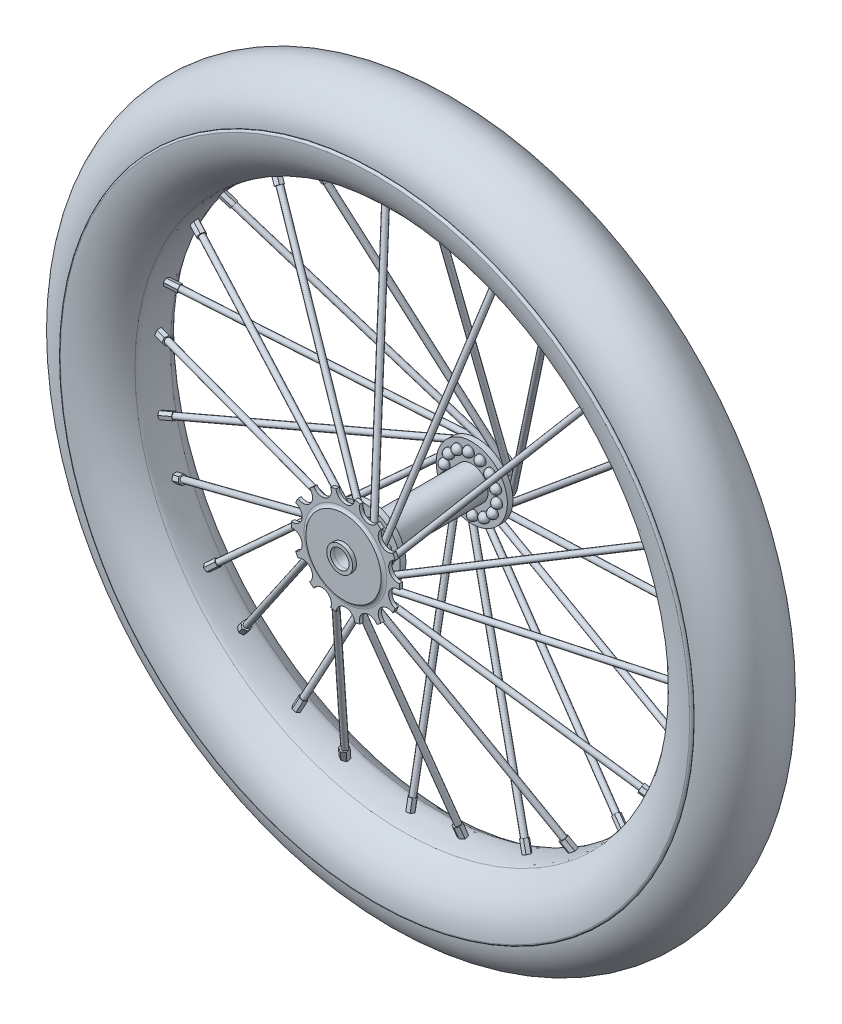
SolidWorks part; units mm, degrees
ref_plane "Front Plane" through (0, 0, 0) normal (0, 0, 1) x (1, 0, 0)
ref_plane "Top Plane" through (0, 0, 0) normal (0, 1, 0) x (1, 0, 0)
ref_plane "Right Plane" through (0, 0, 0) normal (1, 0, 0) x (0, 0, -1)
sketch "Sketch1" plane through (0, 0, 0) normal (1, 0, 0) x (0, 0, -1)
  line L0 (0, 144.78) -> (0, 0) construction
  line L1 (0, 0) -> (80.3154, 0) construction
  line L2 (0, 144.78) -> (0, 170.18) construction
  arc A0 (-22.86, 170.18) -> (22.86, 170.18) centre (0, 170.18) cw
  arc A1 (-22.86, 170.18) -> (-24.892, 170.18) centre (-23.876, 170.18) ccw
  arc A2 (22.86, 170.18) -> (24.892, 170.18) centre (23.876, 170.18) cw
  spline S0 degree 3 poles (-24.892, 170.18) (-24.6538, 159.1982) (-19.5696, 150.8197) (-9.6393, 145.0444) knots 0 0 0 0 1 1 1 1
  spline S1 degree 3 poles (24.892, 170.18) (24.6538, 159.1982) (19.5696, 150.8197) (9.6393, 145.0444) knots 0 0 0 0 1 1 1 1
  spline S2 degree 3 poles (-9.6393, 145.0444) (-7.0831, 143.5577) (7.0625, 143.5457) (9.6393, 145.0444) knots 0 0 0 0 1 1 1 1
  point P12 (0, 143.9249)
  dimension "D3" = 22.86
  dimension "D4" = 1.016
  dimension "D1" = 144.78
  dimension "D2" = 25.4
  dimension "D5" = 0.8551
revolve "Revolve1" add sketch "Sketch1" angle 360 about L1
sketch "Sketch2" plane through (0, 0, 0) normal (0, 0, 1) x (1, 0, 0)
  circle A0 centre (0, 0) radius 8.89
  circle A1 centre (0, 0) radius 5.08
  dimension "D1" = 10.16
  dimension "D2" = 17.78
extrude "Boss-Extrude1" add sketch "Sketch2" along normal blind 38.1 and the other way blind 38.1 separate body
sketch "Sketch3" plane through (0, 0, 38.1) normal (0, 0, 1) x (1, 0, 0)
  line L0 (5.0608, -28.7683) -> (7.9225, -28.1151)
  arc A0 (19.3366, 21.8934) -> (17.0417, 23.7235) centre (0, 0) ccw
  arc A1 (-5.0608, 28.7683) -> (5.0608, 28.7683) centre (0, 29.21) ccw
  arc A2 (7.9225, 28.1151) -> (17.0417, 23.7235) centre (12.6737, 26.3173) ccw
  arc A3 (19.3366, 21.8934) -> (25.6473, 13.9801) centre (22.8373, 18.2121) ccw
  arc A4 (26.9209, 11.3354) -> (29.1731, 1.4677) centre (28.4776, 6.4998) ccw
  arc A5 (29.1731, -1.4677) -> (26.9209, -11.3354) centre (28.4776, -6.4998) ccw
  arc A6 (25.6473, -13.9801) -> (19.3366, -21.8934) centre (22.8373, -18.2121) ccw
  arc A7 (17.0417, -23.7235) -> (7.9225, -28.1151) centre (12.6737, -26.3173) ccw
  arc A8 (5.0608, -28.7683) -> (-5.0608, -28.7683) centre (0, -29.21) ccw
  arc A9 (-7.9225, -28.1151) -> (-17.0417, -23.7235) centre (-12.6737, -26.3173) ccw
  arc A10 (-19.3366, -21.8934) -> (-25.6473, -13.9801) centre (-22.8373, -18.2121) ccw
  arc A11 (-26.9209, -11.3354) -> (-29.1731, -1.4677) centre (-28.4776, -6.4998) ccw
  arc A12 (-29.1731, 1.4677) -> (-26.9209, 11.3354) centre (-28.4776, 6.4998) ccw
  arc A13 (-25.6473, 13.9801) -> (-19.3366, 21.8934) centre (-22.8373, 18.2121) ccw
  arc A14 (-17.0417, 23.7235) -> (-7.9225, 28.1151) centre (-12.6737, 26.3173) ccw
  arc A15 (26.9209, 11.3354) -> (25.6473, 13.9801) centre (0, 0) ccw
  arc A16 (29.1731, -1.4677) -> (29.1731, 1.4677) centre (0, 0) ccw
  arc A17 (25.6473, -13.9801) -> (26.9209, -11.3354) centre (0, 0) ccw
  arc A18 (17.0417, -23.7235) -> (19.3366, -21.8934) centre (0, 0) ccw
  arc A19 (-7.9225, -28.1151) -> (-5.0608, -28.7683) centre (0, 0) ccw
  arc A20 (-19.3366, -21.8934) -> (-17.0417, -23.7235) centre (0, 0) ccw
  arc A21 (-26.9209, -11.3354) -> (-25.6473, -13.9801) centre (0, 0) ccw
  arc A22 (-29.1731, 1.4677) -> (-29.1731, -1.4677) centre (0, 0) ccw
  arc A23 (-25.6473, 13.9801) -> (-26.9209, 11.3354) centre (0, 0) ccw
  arc A24 (-17.0417, 23.7235) -> (-19.3366, 21.8934) centre (0, 0) ccw
  arc A25 (-5.0608, 28.7683) -> (-7.9225, 28.1151) centre (0, 0) ccw
  arc A26 (7.9225, 28.1151) -> (5.0608, 28.7683) centre (0, 0) ccw
  circle A27 centre (0, 0) radius 5.08
  dimension "D1" = 58.42
  dimension "D2" = 10.16
  dimension "D3" = 14
extrude "Boss-Extrude2" add sketch "Sketch3" along normal blind 3.81
sketch "Sketch4" plane through (0, 0, 38.1) normal (0, 0, -1) x (-1, 0, 0)
  circle A0 centre (0, 0) radius 11.43
  circle A1 centre (0, 0) radius 5.08 construction
  circle A2 centre (0, 0) radius 5.08
  dimension "D1" = 22.86
extrude "Boss-Extrude3" add sketch "Sketch4" along normal blind 3.81
sketch "Sketch5" plane through (0, 0, 34.29) normal (0, 0, -1) x (-1, 0, 0)
  circle A0 centre (0, 0) radius 10.16
  circle A1 centre (0, 0) radius 5.08 construction
  circle A2 centre (0, 0) radius 5.08
  dimension "D1" = 20.32
extrude "Boss-Extrude4" add sketch "Sketch5" along normal blind 3.81
mirror "Mirror1" about plane through (0, 0, 0) normal (0, 0, 1) of "Boss-Extrude4", "Boss-Extrude3"
fillet "Fillet1" radius 2.54 2 edges at (10.16, 0, -34.29) (-10.16, 0, 34.29)
sketch "Sketch6" plane through (0, 0, 0) normal (0, 1, 0) x (1, 0, 0)
  line L0 (0, 38.1) -> (0, 0) construction
  line L1 (11.43, 38.1) -> (-11.43, 38.1) construction
  line L2 (-8.89, 30.48) -> (8.89, 30.48) construction
  line L3 (-5.08, 30.48) -> (-19.2403, 30.48)
  line L4 (-5.08, 30.48) -> (-5.08, 27.432)
  line L5 (-5.08, 27.432) -> (-19.2403, 27.432)
  line L6 (-19.2403, 30.48) -> (-19.2403, 27.432)
  line L7 (0, 0) -> (42.2155, 0) construction
  line L8 (-19.2403, -30.48) -> (-19.2403, -27.432)
  line L9 (-5.08, -27.432) -> (-19.2403, -27.432)
  line L10 (-5.08, -30.48) -> (-5.08, -27.432)
  line L11 (-5.08, -30.48) -> (-19.2403, -30.48)
  dimension "D1" = 5.08
  dimension "D2" = 3.048
revolve "Revolve2" add sketch "Sketch6" angle 360 about L0
sketch "Sketch7" plane through (0, 0, 41.91) normal (0, 0, 1) x (1, 0, 0)
  circle A0 centre (0, 0) radius 6.985
  circle A1 centre (0, 0) radius 5.08
  dimension "D1" = 13.97
extrude "Boss-Extrude5" add sketch "Sketch7" along normal blind 2.032 separate body
sketch "Sketch8" plane through (0, 0, -38.1) normal (0, 0, -1) x (-1, 0, 0)
  circle A0 centre (0, 0) radius 5.08 construction
  circle A1 centre (0, 0) radius 5.08
  circle A2 centre (0, 0) radius 6.985
  dimension "D1" = 13.97
extrude "Boss-Extrude6" add sketch "Sketch8" along normal blind 6.35 separate body
sketch3d "3DSketch1"
  line L0 (-1.1255, 14.3103, -27.432) -> (-1.1255, 14.3103, -31.1659)
  line L1 (-4.8438, 14.9579, -34.1261) -> (-138.7457, 38.278, -0.7821)
  line L2 (-1.1255, 14.3103, -27.432) -> (-1.1255, 14.3103, -24.384)
  arc A0 (-4.8438, 14.9579, -34.1261) -> (-1.1255, 14.3103, -31.1659) centre (-4.1283, 14.8333, -31.1659) ccw
  point P0 (-1.1255, 14.3103, -27.432)
  point P1 (-138.7457, 38.278, -0.7821)
  point P7 (-1.1255, 14.3103, -35.052)
  point P8 (-4.6513, 11.8305, -31.1659)
  dimension "D2" = 3.048
  dimension "D1" = 7.62
  dimension "D3" = 3.048
ref_plane "Plane1" through (-138.7457, 38.278, -0.7821) normal (-0.9568, 0.1666, 0.2383) x (0.2347, -0.0409, 0.9712)
sketch "Sketch9" plane through (-138.7457, 38.278, -0.7821) normal (-0.9568, 0.1666, 0.2383) x (0.2347, -0.0409, 0.9712)
  circle A0 centre (0, 0) radius 1.524
  dimension "D1" = 3.048
sweep "Sweep1" add profiles "Sketch9" path "3DSketch1"
sketch "Sketch10" plane through (0, 0, -24.384) normal (0, 0, 1) x (1, 0, 0)
  circle A0 centre (-1.1255, 14.3103) radius 2.54
  dimension "D1" = 5.08
extrude "Boss-Extrude7" add sketch "Sketch10" against normal up to next
sketch "Sketch11" plane through (-138.7457, 38.278, -0.7821) normal (-0.9568, 0.1666, 0.2383) x (0.2347, -0.0409, 0.9712)
  line L1 (-0.3408, -2.0032) -> (1.5644, -1.2967)
  line L2 (1.5644, -1.2967) -> (1.9052, 0.7065)
  line L3 (1.9052, 0.7065) -> (0.3408, 2.0032)
  line L4 (0.3408, 2.0032) -> (-1.5644, 1.2967)
  line L5 (-1.5644, 1.2967) -> (-1.9052, -0.7065)
  line L6 (-1.9052, -0.7065) -> (-0.3408, -2.0032)
  circle A0 centre (0, 0) radius 1.7598 construction
  dimension "D1" = 2.032
extrude "Boss-Extrude8" add sketch "Sketch11" against normal blind 6.35 separate body
pattern_circular "CirPattern1" count 14 over 360 about axis through (0, 0, -38.1) along (0, 0, 1) of "Sweep1", "Boss-Extrude7", "Boss-Extrude8" reverse direction yes
fillet "Fillet2" radius 2.54 14 edges at (-4.9346, 13.5069, -24.384) (-10.3063, 10.0282, -24.384) (-13.6368, 4.5634, -24.384) (-14.2663, -1.8053, -24.384) (-12.0702, -7.8164, -24.384) (-7.4834, -12.2794, -24.384) (-1.4145, -14.3103, -24.384) (4.9346, -13.5069, -24.384) (10.3063, -10.0282, -24.384) (13.6368, -4.5634, -24.384) (14.2663, 1.8053, -24.384) (1.4145, 14.3103, -24.384) (7.4834, 12.2794, -24.384) (12.0702, 7.8164, -24.384)
sketch3d "3DSketch2"
  line L0 (12.9589, 5.3034, 27.432) -> (12.9589, 5.3034, 31.0553)
  line L1 (13.813, 9.0619, 33.9947) -> (42.9772, 137.3914, -2.1051)
  line L2 (12.9589, 5.3034, 27.432) -> (12.9589, 5.3034, 24.384)
  arc A0 (12.9589, 5.3034, 31.0553) -> (13.813, 9.0619, 33.9947) centre (13.6343, 8.2756, 31.0553) ccw
  point P0 (42.9772, 137.3914, -2.1051)
  point P1 (12.9589, 5.3034, 27.432)
  point P7 (12.9589, 5.3034, 35.052)
  point P8 (10.6621, 8.9511, 31.0553)
  point P10 (16.2351, 5.7623, 27.432)
  point P11 (16.6997, 5.49, 27.432)
  point P12 (12.9589, 5.3034, 27.432)
  dimension "D2" = 3.048
  dimension "D1" = 7.62
  dimension "D3" = 3.048
ref_plane "Plane2" through (42.9772, 137.3914, -2.1051) normal (0.2137, 0.9404, -0.2645) x (0.9769, -0.2078, 0.0505)
sketch "Sketch12" plane through (42.9772, 137.3914, -2.1051) normal (0.2137, 0.9404, -0.2645) x (0.9769, -0.2078, 0.0505)
  circle A0 centre (0, 0) radius 1.524
  dimension "D1" = 3.048
sweep "Sweep3" add profiles "Sketch12" path "3DSketch2"
sketch "Sketch14" plane through (0, 0, 24.384) normal (0, 0, -1) x (-1, 0, 0)
  circle A0 centre (-12.9589, 5.3034) radius 2.54
  dimension "D1" = 5.08
extrude "Boss-Extrude10" add sketch "Sketch14" against normal up to next
fillet "Fillet3" radius 2.54 1 edges at (12.9589, 7.8434, 24.384)
sketch "Sketch15" plane through (42.9772, 137.3914, -2.1051) normal (0.2137, 0.9404, -0.2645) x (0.9769, -0.2078, 0.0505)
  line L1 (-1.9646, -1.2838) -> (-0.0164, -2.5054)
  line L2 (-0.0164, -2.5054) -> (2.0156, -1.429)
  line L3 (2.0156, -1.429) -> (2.0994, 0.869)
  line L4 (2.0994, 0.869) -> (0.1512, 2.0906)
  line L5 (0.1512, 2.0906) -> (-1.8808, 1.0142)
  line L6 (-1.8808, 1.0142) -> (-1.9646, -1.2838)
  circle A0 centre (0.0674, -0.2074) radius 1.9914 construction
  dimension "D1" = 2.032
extrude "Boss-Extrude12" add sketch "Sketch15" against normal blind 6.35
pattern_circular "CirPattern3" count 14 over 360 about axis through (0, 0, -38.1) along (0, 0, 1) of "Sweep3", "Fillet3", "Boss-Extrude12", "Boss-Extrude10" reverse direction yes
sketch "Sketch16" plane through (0, 0, 41.91) normal (0, 0, 1) x (1, 0, 0)
  circle A0 centre (0, 0) radius 20.32
  circle A1 centre (0, 0) radius 37.8934
  dimension "D1" = 40.64
extrude "Cut-Extrude1" cut sketch "Sketch16" against normal blind 1.016
fillet "Fillet4" radius 2.54 1 edges at (20.32, 0, 40.894)
sketch "Sketch17" plane through (0, 0, 38.1) normal (0, 0, -1) x (-1, 0, 0)
  circle A1 centre (0, 0) radius 37.8934
  circle A2 centre (0, 0) radius 37.8934
  circle A3 centre (0, 0) radius 20.32
  circle A4 centre (0, 0) radius 20.32
  dimension "D1" = 0
  dimension "D2" = 0
extrude "Cut-Extrude2" cut sketch "Sketch17" against normal blind 1.016
fillet "Fillet5" radius 2.54 1 edges at (-20.32, 0, 38.1)
